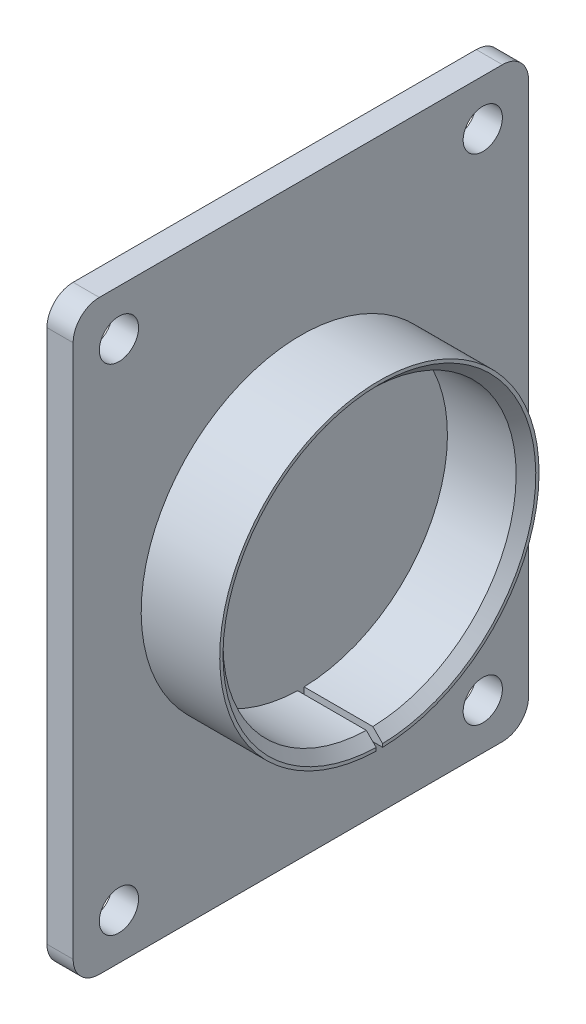
SolidWorks part; units mm, degrees
ref_plane "Front Plane" through (0, 0, 0) normal (1, 0, 0) x (0, 1, 0)
ref_plane "Top Plane" through (0, 0, 0) normal (0, 0, 1) x (0, 1, 0)
ref_plane "Right Plane" through (0, 0, 0) normal (0, 1, 0) x (-1, 0, 0)
sketch "Sketch1" plane through (0, 0, 0) normal (1, 0, 0) x (0, 1, 0)
  line L0 (-12.2, 0) -> (-11.2, 0) construction
  line L1 (-12.1974, -0.25) -> (-11.1972, -0.25)
  line L2 (-12.1974, 0.25) -> (-11.1972, 0.25)
  arc A0 (-11.1972, -0.25) -> (-11.1972, 0.25) centre (0, 0) ccw
  arc A1 (-12.1974, -0.25) -> (-12.1974, 0.25) centre (0, 0) ccw
  dimension "D1" = 22.4
  dimension "D2" = 24.4
  dimension "D3" = 0.5
extrude "Boss-Extrude1" add sketch "Sketch1" along normal blind 6
sketch "Sketch4" plane through (0, 0, 0) normal (-1, 0, 0) x (0, -1, 0)
  line L0 (0, 0) -> (0, 42.7171) construction
  line L1 (0, 0) -> (-46.5379, 0) construction
  line L2 (22.4, -17.4) -> (22.4, 17.4)
  line L4 (-22.4, -17.4) -> (-22.4, 17.4)
  line L5 (-22.4, 17.4) -> (22.4, 17.4)
  line L7 (-22.4, -17.4) -> (22.4, 17.4) construction
  line L8 (-22.4, 17.4) -> (22.4, -17.4) construction
  line L9 (-22.4, -17.4) -> (22.4, -17.4)
  circle A0 centre (-18.9, 13.9) radius 1.5
  circle A1 centre (18.9, 13.9) radius 1.5
  circle A2 centre (-18.9, -13.9) radius 1.5
  circle A3 centre (18.9, -13.9) radius 1.5
  point P13 (-22.4, 0)
  point P14 (0, 17.4)
  point P15 (22.4, 0)
  dimension "D1" = 3
  dimension "D2" = 37.8
  dimension "D3" = 27.8
  dimension "D4" = 2
  dimension "D5" = 2
extrude "Boss-Extrude3" add sketch "Sketch4" along normal blind 2
fillet "Fillet1" radius 2 4 edges at (-1, -22.4, 17.4) (-1, -22.4, -17.4) (-1, 22.4, -17.4) (-1, 22.4, 17.4)
chamfer "Chamfer1" distance 0.75 angle 45 1 edges at (6, 11.2, 0)
